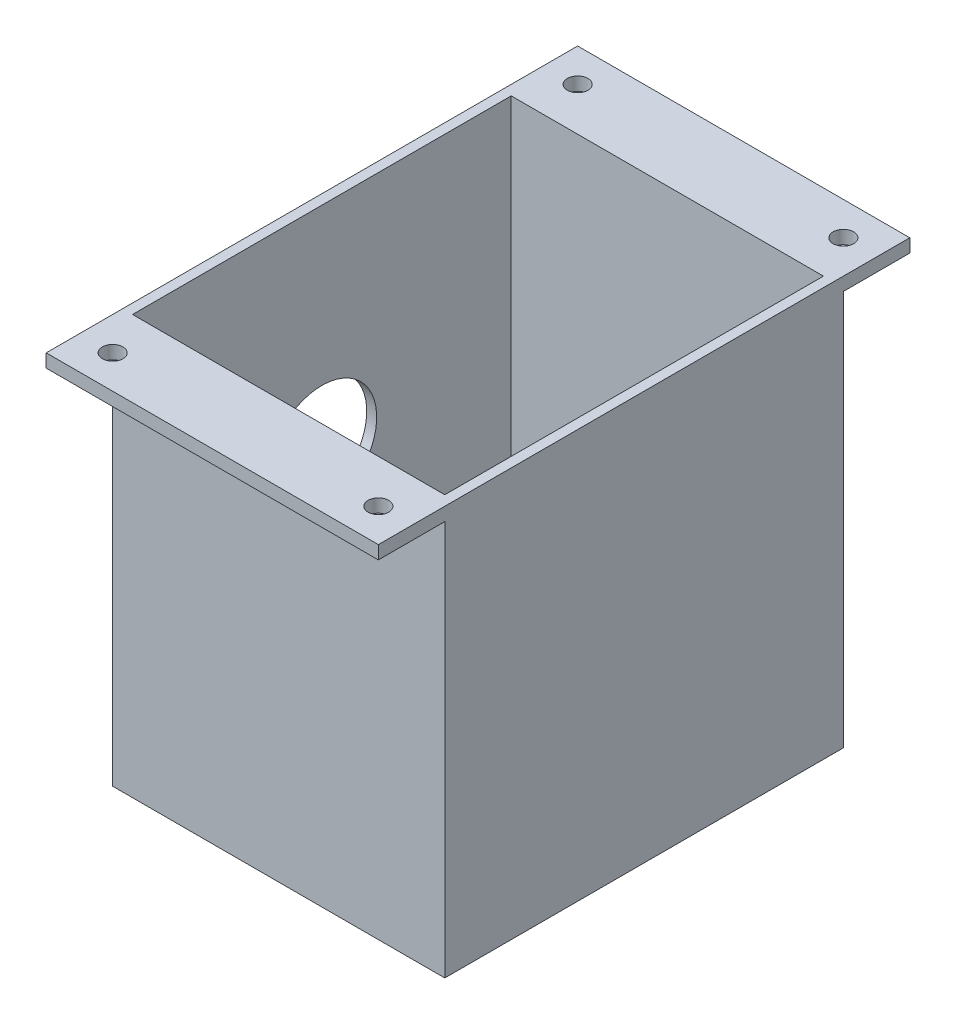
SolidWorks part; units mm, degrees
ref_plane "Płaszczyzna przednia" through (0, 0, 0) normal (0, 0, 1) x (1, 0, 0)
ref_plane "Płaszczyzna górna" through (0, 0, 0) normal (0, 1, 0) x (1, 0, 0)
ref_plane "Płaszczyzna prawa" through (0, 0, 0) normal (1, 0, 0) x (0, 0, -1)
sketch "Sketch1" plane through (0, 0, 0) normal (0, 1, 0) x (1, 0, 0)
  line L9 (-25, -40) -> (25, -40)
  line L16 (-25, -40) -> (-25, 40)
  line L21 (-25, 40) -> (25, 40)
  line L23 (25, -40) -> (25, 40)
  line L24 (-23.5, -28.5) -> (23.5, -28.5)
  line L25 (-23.5, -28.5) -> (-23.5, 28.5)
  line L26 (-25, -30) -> (25, -30)
  line L27 (-25, -30) -> (-25, 30)
  line L28 (-25, 30) -> (25, 30)
  line L29 (25, -30) -> (25, 30)
  line L30 (-23.5, 28.5) -> (23.5, 28.5)
  line L31 (23.5, -28.5) -> (23.5, 28.5)
  line L32 (-23.5, -28.5) -> (23.5, 28.5) construction
  line L33 (-23.5, 28.5) -> (23.5, -28.5) construction
  point P0 (0, 0)
  point P1 (0, 0)
  point P5 (0, 0)
  point P8 (0, 0)
  point P11 (0, 0)
  point P14 (0, 0)
  dimension "D1" = 50
  dimension "D2" = 80
  dimension "D3" = 50
  dimension "D4" = 60
  dimension "D5" = 47
  dimension "D6" = 57
extrude "Boss-Extrude6" add sketch "Sketch1" along normal blind 60 contours L28 L16 L26 L23 L31 L24 L25 L30 region at (-24.219, 0, 0)
sketch "Sketch7" plane through (0, 0, 0) normal (0, -1, 0) x (1, 0, 0)
  line L1 (-25, 30) -> (25, 30)
  line L2 (-25, 30) -> (-25, -30)
  line L3 (-25, -30) -> (25, -30)
  line L4 (25, 30) -> (25, -30)
extrude "Boss-Extrude8" add sketch "Sketch7" along normal blind 1.5
sketch "Sketch8" plane through (25, 0, 0) normal (1, 0, 0) x (0, 0, -1)
  line L1 (-30, 60) -> (-40, 60)
  line L2 (-30, 60) -> (-30, 58)
  line L3 (-30, 58) -> (-40, 58)
  line L4 (-40, 60) -> (-40, 58)
  line L5 (30, 60) -> (40, 60)
  line L6 (30, 60) -> (30, 58)
  line L7 (30, 58) -> (40, 58)
  line L8 (40, 60) -> (40, 58)
  dimension "D1" = 10
  dimension "D2" = 2
  dimension "D3" = 10
  dimension "D4" = 2
extrude "Boss-Extrude9" add sketch "Sketch8" against normal blind 50
sketch "Sketch9" plane through (0, 60, 0) normal (0, 1, 0) x (1, 0, 0)
  circle A0 centre (-20, 35) radius 1.55
  circle A1 centre (20, 35) radius 1.55
  circle A2 centre (20, -35) radius 1.55
  circle A3 centre (-20, -35) radius 1.55
  point P0 (0, 0)
  dimension "D1" = 40
  dimension "D2" = 70
extrude "Cut-Extrude1" cut sketch "Sketch9" against normal blind 3
sketch "Sketch11" plane through (-25, 0, 0) normal (-1, 0, 0) x (0, 0, 1)
  line L0 (-30, 28.25) -> (30, 28.25) construction
  line L1 (-30, 58) -> (-30, -1.5) construction
  line L2 (30, 58) -> (30, -1.5) construction
  line L4 (40, 60) -> (-40, 60) construction
  line L5 (0, 60) -> (0, -1.5) construction
  line L6 (30, -1.5) -> (-30, -1.5) construction
  circle A0 centre (0, 28.25) radius 8.25
  point P6 (0, 28.25)
extrude "Cut-Extrude3" cut sketch "Sketch11" against normal blind 1.5
